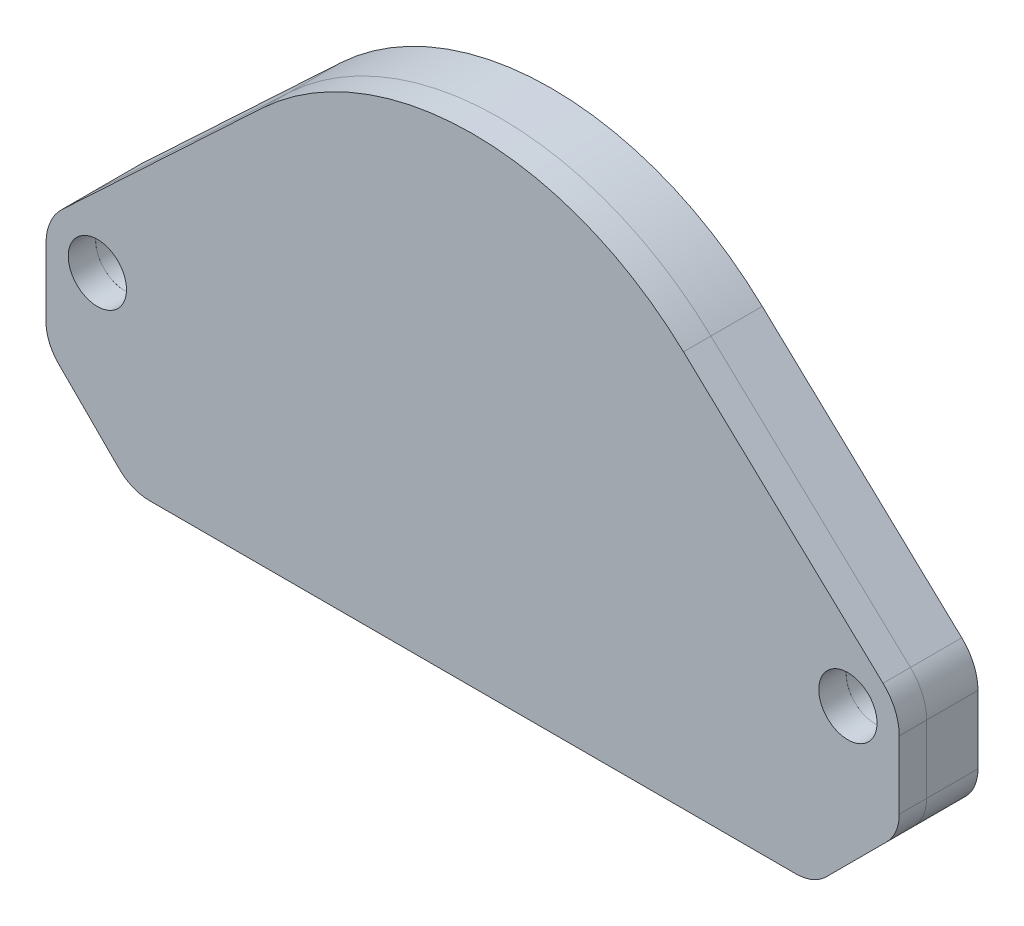
SolidWorks part; units mm, degrees
other "Spacer"
ref_plane "Front Plane" through (0, 0, 0) normal (0, 0, 1) x (1, 0, 0)
ref_plane "Top Plane" through (0, 0, 0) normal (0, 1, 0) x (1, 0, 0)
ref_plane "Right Plane" through (0, 0, 0) normal (1, 0, 0) x (0, 0, -1)
sketch "Sketch1" plane through (0, 0, 0) normal (0, 0, 1) x (1, 0, 0)
  line L0 (-12.3175, 13.1255) -> (-23.9729, 2.1876)
  line L1 (12.3175, 13.1255) -> (23.9729, 2.1876)
  line L2 (-21.92, 0) -> (21.92, 0) construction
  line L3 (-24.92, 0) -> (-24.92, -10)
  line L4 (-24.92, -10) -> (24.92, -10)
  line L5 (0, -10) -> (0, 0) construction
  line L6 (24.92, 0) -> (24.92, -10)
  arc A1 (-23.9729, 2.1876) -> (-24.92, 0) centre (-21.92, 0) ccw
  arc A2 (24.92, 0) -> (23.9729, 2.1876) centre (21.92, 0) ccw
  circle A3 centre (-21.92, 0) radius 1.7
  circle A4 centre (21.92, 0) radius 1.7
  arc A5 (12.3175, 13.1255) -> (-12.3175, 13.1255) centre (0, 0) ccw
  dimension "D1" = 43.84
  dimension "D2" = 18
  dimension "D3" = 6
  dimension "D5" = 3.4
  dimension "D4" = 10
extrude "Boss-Extrude1" add sketch "Sketch1" along normal blind 1.6
chamfer "Chamfer1" distance 5 angle 45 2 edges at (-24.92, -10, 0.8) (24.92, -10, 0.8)
fillet "Fillet1" radius 2.5 4 edges at (19.92, -10, 0.8) (24.92, -5, 0.8) (-19.92, -10, 0.8) (-24.92, -5, 0.8)
sketch "Sketch2" plane through (0, 0, 0) normal (0, 0, -1) x (-1, 0, 0)
  line L7 (-17.72, 0) -> (-17.72, -8)
  line L8 (17.72, 0) -> (17.72, -8)
  line L9 (-16.2662, 6.6772) -> (-10, 0) construction
  line L10 (-10, 0) -> (-10, -8) construction
  line L11 (-17.3599, 5.6507) -> (-11.5, -0.5936)
  line L12 (-11.5, -0.5936) -> (-11.5, -8)
  line L13 (-15.1724, 7.7036) -> (-8.5, 0.5936)
  line L14 (-22.7736, -4.318) -> (-19.238, -7.8536)
  line L15 (-18.8845, -8) -> (18.8845, -8)
  line L16 (19.238, -7.8536) -> (22.7736, -4.318)
  line L17 (22.92, -3.9645) -> (22.92, 0)
  line L18 (22.6043, 0.7292) -> (10.9489, 11.6671)
  line L19 (-10.9489, 11.6671) -> (-22.6043, 0.7292)
  line L20 (-22.92, 0) -> (-22.92, -3.9645)
  line L21 (-22.7736, -4.318) -> (-19.238, -7.8536)
  line L22 (-18.8845, -8) -> (18.8845, -8)
  line L23 (19.238, -7.8536) -> (22.7736, -4.318)
  line L24 (22.92, -3.9645) -> (22.92, 0)
  line L25 (22.6043, 0.7292) -> (10.9489, 11.6671)
  line L26 (-10.9489, 11.6671) -> (-22.6043, 0.7292)
  line L27 (-22.92, 0) -> (-22.92, -3.9645)
  line L28 (-24.1878, -5.7322) -> (-20.6522, -9.2678)
  line L29 (-18.8845, -10) -> (18.8845, -10)
  line L30 (20.6522, -9.2678) -> (24.1878, -5.7322)
  line L31 (24.92, -3.9645) -> (24.92, 0)
  line L32 (23.9729, 2.1876) -> (12.3175, 13.1255)
  line L33 (-12.3175, 13.1255) -> (-23.9729, 2.1876)
  line L34 (-24.92, 0) -> (-24.92, -3.9645)
  line L35 (-24.1878, -5.7322) -> (-20.6522, -9.2678)
  line L36 (-18.8845, -10) -> (18.8845, -10)
  line L37 (20.6522, -9.2678) -> (24.1878, -5.7322)
  line L38 (24.92, -3.9645) -> (24.92, 0)
  line L39 (23.9729, 2.1876) -> (12.3175, 13.1255)
  line L40 (-12.3175, 13.1255) -> (-23.9729, 2.1876)
  line L41 (-24.92, 0) -> (-24.92, -3.9645)
  line L42 (-8.5, 0.5936) -> (-8.5, -8)
  line L43 (0, 0) -> (0, -8) construction
  line L44 (8.5, 0.5936) -> (8.5, -8)
  line L45 (10, 0) -> (10, -8) construction
  line L46 (11.5, -0.5936) -> (11.5, -8)
  line L47 (17.3599, 5.6507) -> (11.5, -0.5936)
  line L48 (16.2662, 6.6772) -> (10, 0) construction
  line L49 (15.1724, 7.7036) -> (8.5, 0.5936)
  arc A14 (22.92, 0) -> (22.6043, 0.7292) centre (21.92, 0) ccw
  arc A15 (10.9489, 11.6671) -> (-10.9489, 11.6671) centre (0, 0) ccw
  arc A16 (-22.6043, 0.7292) -> (-22.92, 0) centre (-21.92, 0) ccw
  arc A17 (22.92, 0) -> (22.6043, 0.7292) centre (21.92, 0) ccw
  arc A18 (10.9489, 11.6671) -> (-10.9489, 11.6671) centre (0, 0) ccw
  arc A19 (-22.6043, 0.7292) -> (-22.92, 0) centre (-21.92, 0) ccw
  circle A20 centre (-21.92, 0) radius 4.2
  circle A21 centre (-21.92, 0) radius 4.2
  circle A23 centre (21.92, 0) radius 4.2
  circle A24 centre (21.92, 0) radius 4.2
  arc A31 (-20.6522, -9.2678) -> (-18.8845, -10) centre (-18.8845, -7.5) ccw
  arc A32 (18.8845, -10) -> (20.6522, -9.2678) centre (18.8845, -7.5) ccw
  arc A33 (24.1878, -5.7322) -> (24.92, -3.9645) centre (22.42, -3.9645) ccw
  arc A34 (24.92, 0) -> (23.9729, 2.1876) centre (21.92, 0) ccw
  arc A35 (12.3175, 13.1255) -> (-12.3175, 13.1255) centre (0, 0) ccw
  arc A36 (-23.9729, 2.1876) -> (-24.92, 0) centre (-21.92, 0) ccw
  arc A37 (-24.92, -3.9645) -> (-24.1878, -5.7322) centre (-22.42, -3.9645) ccw
  arc A38 (-20.6522, -9.2678) -> (-18.8845, -10) centre (-18.8845, -7.5) ccw
  arc A39 (18.8845, -10) -> (20.6522, -9.2678) centre (18.8845, -7.5) ccw
  arc A40 (24.1878, -5.7322) -> (24.92, -3.9645) centre (22.42, -3.9645) ccw
  arc A41 (24.92, 0) -> (23.9729, 2.1876) centre (21.92, 0) ccw
  arc A42 (12.3175, 13.1255) -> (-12.3175, 13.1255) centre (0, 0) ccw
  arc A43 (-23.9729, 2.1876) -> (-24.92, 0) centre (-21.92, 0) ccw
  arc A44 (-24.92, -3.9645) -> (-24.1878, -5.7322) centre (-22.42, -3.9645) ccw
  arc A45 (-19.238, -7.8536) -> (-18.8845, -8) centre (-18.8845, -7.5) ccw
  arc A46 (-19.238, -7.8536) -> (-18.8845, -8) centre (-18.8845, -7.5) ccw
  arc A47 (18.8845, -8) -> (19.238, -7.8536) centre (18.8845, -7.5) ccw
  arc A48 (18.8845, -8) -> (19.238, -7.8536) centre (18.8845, -7.5) ccw
  arc A49 (22.7736, -4.318) -> (22.92, -3.9645) centre (22.42, -3.9645) ccw
  arc A50 (22.7736, -4.318) -> (22.92, -3.9645) centre (22.42, -3.9645) ccw
  arc A51 (-22.92, -3.9645) -> (-22.7736, -4.318) centre (-22.42, -3.9645) ccw
  arc A52 (-22.92, -3.9645) -> (-22.7736, -4.318) centre (-22.42, -3.9645) ccw
  line M27 (-24.1878, -5.7322) -> (-20.6522, -9.2678)
  arc M28 (-20.6522, -9.2678) -> (-18.8845, -10) centre (-18.8845, -7.5) ccw
  line M29 (-18.8845, -10) -> (18.8845, -10)
  arc M30 (18.8845, -10) -> (20.6522, -9.2678) centre (18.8845, -7.5) ccw
  line M31 (20.6522, -9.2678) -> (24.1878, -5.7322)
  arc M32 (24.1878, -5.7322) -> (24.92, -3.9645) centre (22.42, -3.9645) ccw
  line M33 (24.92, -3.9645) -> (24.92, 0)
  arc M34 (24.92, 0) -> (23.9729, 2.1876) centre (21.92, 0) ccw
  line M35 (23.9729, 2.1876) -> (12.3175, 13.1255)
  arc M36 (12.3175, 13.1255) -> (-12.3175, 13.1255) centre (0, 0) ccw
  line M37 (-12.3175, 13.1255) -> (-23.9729, 2.1876)
  arc M38 (-23.9729, 2.1876) -> (-24.92, 0) centre (-21.92, 0) ccw
  line M39 (-24.92, 0) -> (-24.92, -3.9645)
  arc M40 (-24.92, -3.9645) -> (-24.1878, -5.7322) centre (-22.42, -3.9645) ccw
  circle M41 centre (21.92, 0) radius 1.7
  circle M42 centre (-21.92, 0) radius 1.7
  dimension "D5" = 1.5
  dimension "D7" = 10
  dimension "D1" = 2
  dimension "D2" = 2.5
  dimension "D3" = 2.5
  dimension "D4" = 0
  dimension "D6" = 1.5
extrude "Boss-Extrude2" add sketch "Sketch2" along normal blind 3 separate body contours A24 L39 A21 L26 A18 L25 M36 M37 | L26 A21 L40 L21 L27 M38 M39 M42 | A24 L23 L22 L21 A21 L41 M40 M27 M28 M29 M30 M31 M32 M33 | L21 A21 L26 L27 M42 | L25 A24 L23 L24 M41 | A24 L25 L24 L23 L38 M35 M41 M34 | A21 A52 L21 A46 L22 L7 | L23 A50 A24 L8 L22 A48 | L25 L49 L44 L22 L46 L47 | L42 L13 L26 L11 L12 L22 region at (20.0328, -0.8169, 0) region at (19.3411, -5.1525, 0) region at (0, -8.3253, 0) region at (20.5467, 4.453, 0) region at (20.683, 2.667, 0) region at (11.6399, -0.0705, 0) region at (-11.6399, -0.0705, 0) region at (-22.834, 3.1216, 0) region at (-19.3411, -5.1525, 0) region at (-20.0328, -0.8169, 0)
sketch "Sketch3" plane through (0, 0, 0) normal (0, 0, 1) x (1, 0, 0)
  line L0 (0, 0) -> (0, 18) construction
  circle A0 centre (-6.85, 13.3) radius 2
  arc A1 (12.3175, 13.1255) -> (-12.3175, 13.1255) centre (0, 0) ccw construction
  circle A2 centre (6.85, 13.3) radius 2
  point P10 (-8.2517, 13.3)
  point P11 (0, 0)
  dimension "D1" = 13.3
  dimension "D3" = 4
  dimension "D2" = 13.7
extrude "Cut-Extrude1" cut sketch "Sketch3" against normal through all draft 20
fillet "Fillet2" radius 1.5 18 edges at (19.6298, 3.5206, -1.5) (-19.6298, 3.5206, -1.5) (-8.5, -8, -1.5) (-8.5, 0.5936, -1.5) (-15.1724, 7.7036, -1.5) (15.1724, 7.7036, -1.5) (8.5, 0.5936, -1.5) (8.5, -8, -1.5) (-17.3599, 5.6507, -1.5) (-11.5, -0.5936, -1.5) (-11.5, -8, -1.5) (-17.72, -8, -1.5) (17.72, -8, -1.5) (11.5, -8, -1.5) (11.5, -0.5936, -1.5) (17.3599, 5.6507, -1.5) (7.2168, 14.28, -2.6201) (-7.4348, 14.1677, -2.6201)
